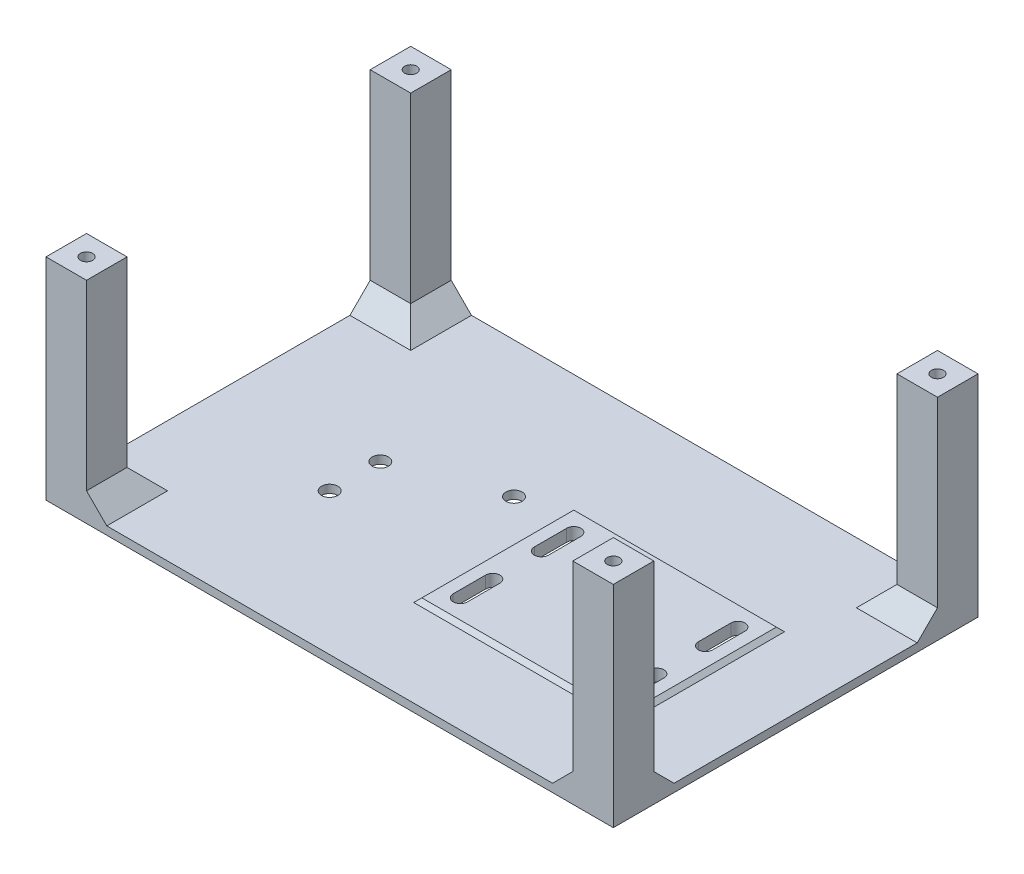
SolidWorks part; units mm, degrees
ref_plane "Front Plane" through (0, 0, 0) normal (0, 0, 1) x (1, 0, 0)
ref_plane "Top Plane" through (0, 0, 0) normal (0, 1, 0) x (1, 0, 0)
ref_plane "Right Plane" through (0, 0, 0) normal (1, 0, 0) x (0, 0, -1)
sketch "Sketch1" plane through (0, 0, 0) normal (0, 1, 0) x (1, 0, 0)
  line L1 (70, -45) -> (-70, -45)
  line L2 (70, -45) -> (70, 45)
  line L3 (70, 45) -> (-70, 45)
  line L4 (-70, -45) -> (-70, 45)
  line L5 (70, -45) -> (-70, 45) construction
  line L6 (70, 45) -> (-70, -45) construction
  point P0 (0, 0)
  dimension "D1" = 90
  dimension "D2" = 140
extrude "Boss-Extrude1" add sketch "Sketch1" along normal blind 2
sketch "Sketch2" plane through (0, 2, 0) normal (0, 1, 0) x (1, 0, 0)
  line L0 (-35, -10) -> (-35, 11.5) construction
  line L5 (-35, 11.5) -> (-11, 11.5) construction
  line L12 (-70, -45) -> (70, -45) construction
  line L13 (-70, 45) -> (-70, -45) construction
  circle A7 centre (-35, -10) radius 2
  circle A9 centre (-35, 2.5) radius 2
  circle A10 centre (-11, 11.5) radius 2
  dimension "D1" = 4
  dimension "D2" = 12.5
  dimension "D3" = 24
  dimension "D4" = 9
  dimension "D5" = 35
  dimension "D6" = 35
extrude "Cut-Extrude1" cut sketch "Sketch2" against normal through all
sketch "Sketch3" plane through (0, 2, 0) normal (0, 1, 0) x (1, 0, 0)
  line L0 (-35, 2.5) -> (-35, -10) construction
  line L1 (5, -13.75) -> (45.5, -13.75) construction
  line L2 (5, -13.75) -> (5, 6.25) construction
  line L3 (5, 6.25) -> (45.5, 6.25) construction
  line L4 (45.5, -13.75) -> (45.5, 6.25) construction
  line L5 (5, -13.75) -> (45.5, 6.25) construction
  line L6 (5, 6.25) -> (45.5, -13.75) construction
  circle A0 centre (45.5, 6.25) radius 1.75
  circle A1 centre (45.5, -13.75) radius 1.75
  circle A2 centre (5, 6.25) radius 1.75
  circle A3 centre (5, -13.75) radius 1.75
  point P0 (25.25, -3.75)
  point P13 (-35, -3.75)
  dimension "D1" = 3.5
  dimension "D2" = 40.5
  dimension "D3" = 20
  dimension "D4" = 40
extrude "Cut-Extrude2" cut sketch "Sketch3" against normal through all
sketch "Sketch4" plane through (0, 2, 0) normal (0, 1, 0) x (1, 0, 0)
  line L1 (-70, 45) -> (-60, 45)
  line L2 (-70, 45) -> (-70, 35)
  line L3 (-70, 35) -> (-60, 35)
  line L4 (-60, 45) -> (-60, 35)
  line L5 (70, 45) -> (60, 45)
  line L6 (70, 45) -> (70, 35)
  line L7 (70, 35) -> (60, 35)
  line L8 (60, 45) -> (60, 35)
  line L9 (70, -45) -> (60, -45)
  line L10 (70, -45) -> (70, -35)
  line L11 (70, -35) -> (60, -35)
  line L12 (60, -45) -> (60, -35)
  line L13 (-70, -45) -> (-60, -45)
  line L14 (-70, -45) -> (-70, -35)
  line L15 (-70, -35) -> (-60, -35)
  line L16 (-60, -45) -> (-60, -35)
  dimension "D1" = 10
extrude "Boss-Extrude2" add sketch "Sketch4" along normal blind 50
chamfer "Chamfer1" distance 5 angle 45 8 edges at (65, 2, 35) (60, 2, 40) (-65, 2, 35) (-60, 2, 40) (65, 2, -35) (60, 2, -40) (-65, 2, -35) (-60, 2, -40)
sketch "Sketch6" plane through (0, 52, 0) normal (0, 1, 0) x (1, 0, 0)
  line L0 (-70, 45) -> (-60, 35) construction
  line L1 (70, 45) -> (60, 35) construction
  line L2 (70, -45) -> (60, -35) construction
  line L3 (-70, -45) -> (-60, -35) construction
  circle A0 centre (-65, 40) radius 1.5
  circle A1 centre (65, 40) radius 1.5
  circle A2 centre (65, -40) radius 1.5
  circle A3 centre (-65, -40) radius 1.5
  dimension "D1" = 3
extrude "Cut-Extrude3" cut sketch "Sketch6" against normal through all
sketch "Sketch7" plane through (0, 2, 0) normal (0, 1, 0) x (1, 0, 0)
  line L0 (5, 10.25) -> (5, 2.25) construction
  line L1 (6.75, 10.25) -> (6.75, 2.25)
  line L2 (3.25, 10.25) -> (3.25, 2.25)
  line L3 (45.5, 10.25) -> (45.5, 2.25) construction
  line L4 (47.25, 10.25) -> (47.25, 2.25)
  line L5 (43.75, 10.25) -> (43.75, 2.25)
  line L6 (5, -9.75) -> (5, -17.75) construction
  line L7 (6.75, -9.75) -> (6.75, -17.75)
  line L8 (3.25, -9.75) -> (3.25, -17.75)
  line L9 (45.5, -17.75) -> (45.5, -9.75) construction
  line L10 (43.75, -17.75) -> (43.75, -9.75)
  line L11 (47.25, -17.75) -> (47.25, -9.75)
  arc A0 (6.75, 10.25) -> (3.25, 10.25) centre (5, 10.25) ccw
  arc A1 (3.25, 2.25) -> (6.75, 2.25) centre (5, 2.25) ccw
  arc A2 (47.25, 10.25) -> (43.75, 10.25) centre (45.5, 10.25) ccw
  arc A3 (43.75, 2.25) -> (47.25, 2.25) centre (45.5, 2.25) ccw
  arc A4 (6.75, -9.75) -> (3.25, -9.75) centre (5, -9.75) ccw
  arc A5 (3.25, -17.75) -> (6.75, -17.75) centre (5, -17.75) ccw
  arc A6 (43.75, -17.75) -> (47.25, -17.75) centre (45.5, -17.75) ccw
  arc A7 (47.25, -9.75) -> (43.75, -9.75) centre (45.5, -9.75) ccw
  circle A8 centre (5, 6.25) radius 1.75 construction
  circle A9 centre (45.5, 6.25) radius 1.75 construction
  point P2 (5, 6.25)
  point P7 (45.5, 6.25)
  point P14 (5, -13.75)
  point P21 (45.5, -13.75)
  dimension "D1" = 8
extrude "Cut-Extrude4" cut sketch "Sketch7" against normal through all
sketch "Sketch8" plane through (0, 2, 0) normal (0, 1, 0) x (1, 0, 0)
  line L0 (5, 10.25) -> (45.5, -17.75) construction
  line L1 (50.25, -22.5) -> (0.25, -22.5)
  line L2 (50.25, -22.5) -> (50.25, 15)
  line L3 (50.25, 15) -> (0.25, 15)
  line L4 (0.25, -22.5) -> (0.25, 15)
  line L5 (50.25, -22.5) -> (0.25, 15) construction
  line L6 (50.25, 15) -> (0.25, -22.5) construction
  line L7 (3.25, 10.25) -> (3.25, 2.25) construction
  line L9 (-978.1891, 12) -> (49021.8109, 12) construction
  line L10 (47.25, 2.25) -> (47.25, 10.25) construction
  line L11 (43.75, 10.25) -> (43.75, 2.25) construction
  line L12 (6.75, 2.25) -> (6.75, 10.25) construction
  line L13 (47.25, 2.25) -> (47.25, 10.25)
  line L14 (43.75, 10.25) -> (43.75, 2.25)
  line L15 (3.25, 10.25) -> (3.25, 2.25)
  line L16 (6.75, 2.25) -> (6.75, 10.25)
  line L17 (3.25, -9.75) -> (3.25, -17.75) construction
  line L18 (47.25, -17.75) -> (47.25, -9.75) construction
  line L19 (43.75, -9.75) -> (43.75, -17.75) construction
  line L20 (6.75, -17.75) -> (6.75, -9.75) construction
  line L21 (47.25, -17.75) -> (47.25, -9.75)
  line L22 (43.75, -9.75) -> (43.75, -17.75)
  line L23 (3.25, -9.75) -> (3.25, -17.75)
  line L24 (6.75, -17.75) -> (6.75, -9.75)
  arc A0 (6.75, 10.25) -> (3.25, 10.25) centre (5, 10.25) ccw construction
  arc A1 (43.75, 2.25) -> (47.25, 2.25) centre (45.5, 2.25) ccw construction
  arc A2 (47.25, 10.25) -> (43.75, 10.25) centre (45.5, 10.25) ccw construction
  arc A3 (3.25, 2.25) -> (6.75, 2.25) centre (5, 2.25) ccw construction
  arc A4 (43.75, 2.25) -> (47.25, 2.25) centre (45.5, 2.25) ccw
  arc A5 (47.25, 10.25) -> (43.75, 10.25) centre (45.5, 10.25) ccw
  arc A6 (6.75, 10.25) -> (3.25, 10.25) centre (5, 10.25) ccw
  arc A7 (3.25, 2.25) -> (6.75, 2.25) centre (5, 2.25) ccw
  arc A8 (47.25, -9.75) -> (43.75, -9.75) centre (45.5, -9.75) ccw construction
  arc A9 (43.75, -17.75) -> (47.25, -17.75) centre (45.5, -17.75) ccw construction
  arc A10 (3.25, -17.75) -> (6.75, -17.75) centre (5, -17.75) ccw construction
  arc A11 (6.75, -9.75) -> (3.25, -9.75) centre (5, -9.75) ccw construction
  arc A12 (47.25, -9.75) -> (43.75, -9.75) centre (45.5, -9.75) ccw
  arc A13 (43.75, -17.75) -> (47.25, -17.75) centre (45.5, -17.75) ccw
  arc A14 (3.25, -17.75) -> (6.75, -17.75) centre (5, -17.75) ccw
  arc A15 (6.75, -9.75) -> (3.25, -9.75) centre (5, -9.75) ccw
  point P0 (25.25, -3.75)
  point P9 (25.25, -3.75)
  dimension "D1" = 3
  dimension "D2" = 3
extrude "Boss-Extrude3" add sketch "Sketch8" along normal blind 1
chamfer "Chamfer2" distance 1 angle 45 4 edges at (50.25, 2, 3.75) (25.25, 2, -15) (0.25, 2, 3.75) (25.25, 2, 22.5)
